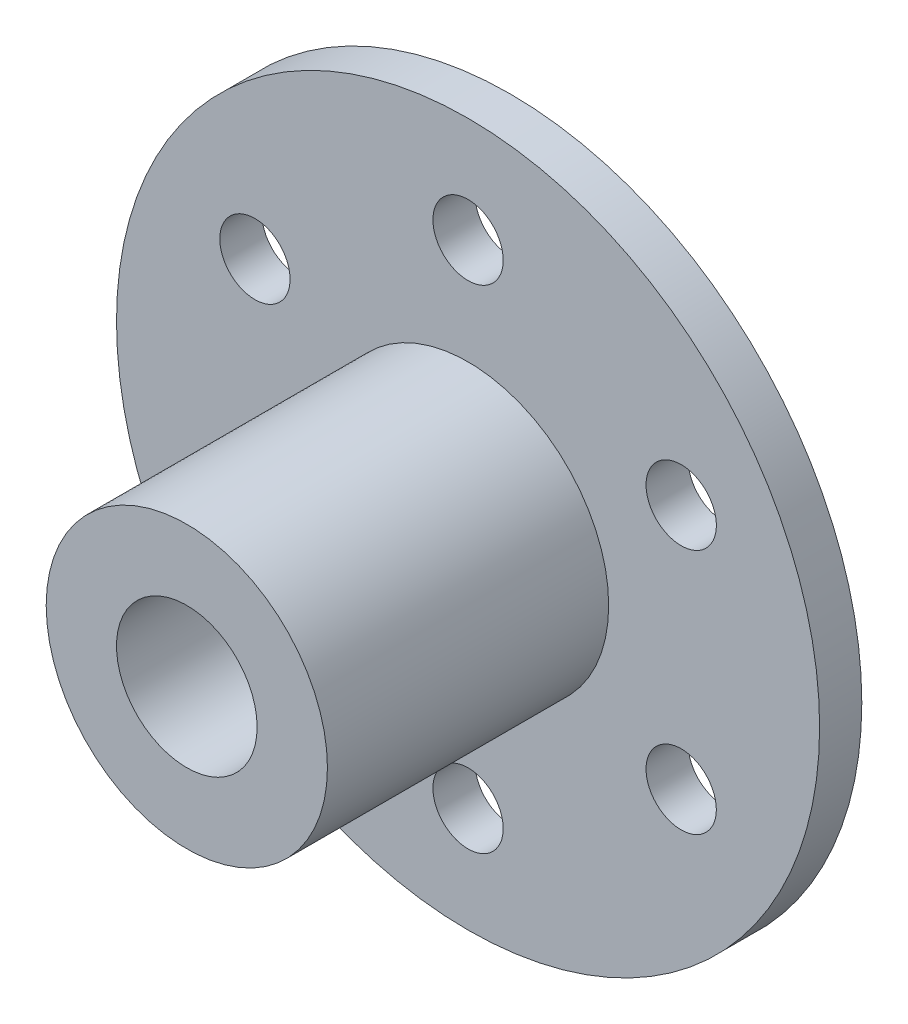
SolidWorks part; units mm, degrees
ref_plane "Front Plane" through (0, 0, 0) normal (0, 0, 1) x (1, 0, 0)
ref_plane "Top Plane" through (0, 0, 0) normal (0, 1, 0) x (1, 0, 0)
ref_plane "Right Plane" through (0, 0, 0) normal (1, 0, 0) x (0, 0, -1)
sketch "Sketch1" plane through (0, 0, 0) normal (0, 0, 1) x (1, 0, 0)
  circle A0 centre (0, 0) radius 50
  circle A1 centre (0, 0) radius 20
  circle A2 centre (0, 0) radius 10
  circle A3 centre (0, 35) radius 5
  circle A4 centre (0, 0) radius 35 construction
  dimension "Outer Flange Diameter" = 100
  dimension "Bolt Circle Diameter" = 70
  dimension "Raise Face Diameter" = 40
  dimension "Nominal Shaft Diameter" = 20
  dimension "Hole Diameter" = 10
extrude "Boss-Extrude1" add sketch "Sketch1" against normal blind 6 contours A0 A3 A1 | A3 | A1 A2 region at (-48.5858, 0, 0) region at (-19.4343, 0, 0) region at (0, 35, 0)
extrude "Boss-Extrude2" add sketch "Sketch1<3>" along normal blind 40 separate body contours A1 A2 region at (-19.4343, 0, 0)
sketch "Sketch1<3>" plane through (0, 0, 0) normal (0, 0, 1) x (1, 0, 0) same geometry as "Sketch1"
extrude "Cut-Extrude1" cut sketch "Sketch1<4>" against normal through all contours A3 region at (0, 35, 0)
sketch "Sketch1<4>" plane through (0, 0, 0) normal (0, 0, 1) x (1, 0, 0) same geometry as "Sketch1"
pattern_circular "CirPattern1" count 6 over 360 about axis through (0, 0, 40) along (0, 0, -1) of "Cut-Extrude1" reverse direction yes
